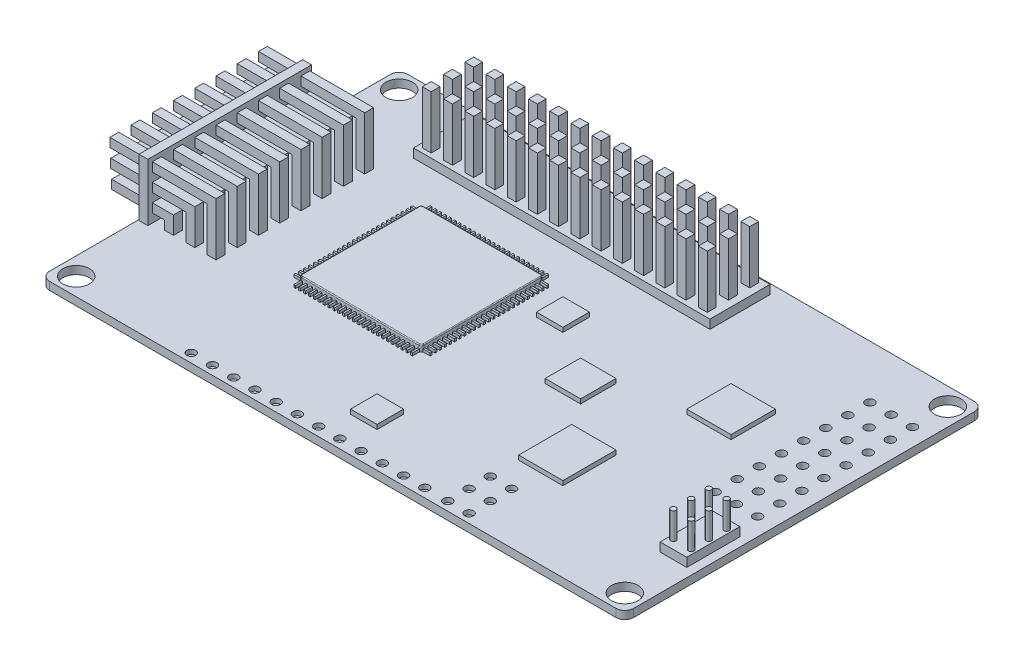
SolidWorks part; units mm, degrees
ref_plane "Спереди" through (0, 0, 0) normal (0, 0, 1) x (1, 0, 0)
ref_plane "Сверху" through (0, 0, 0) normal (0, 1, 0) x (1, 0, 0)
ref_plane "Справа" through (0, 0, 0) normal (1, 0, 0) x (0, 0, -1)
sketch "Эскиз1" plane through (0, 0, 0) normal (0, 1, 0) x (1, 0, 0)
  line L1 (-33, 20.25) -> (33, 20.25)
  line L2 (-33, 20.25) -> (-33, -20.25)
  line L3 (-33, -20.25) -> (33, -20.25)
  line L4 (33, 20.25) -> (33, -20.25)
  dimension "D1" = 66
  dimension "D2" = 40.5
  dimension "D3" = 33
  dimension "D4" = 20.25
extrude "Бобышка-Вытянуть1" add sketch "Эскиз1" along normal blind 0.9
sketch "Эскиз2" plane through (0, 0.9, 0) normal (0, 1, 0) x (1, 0, 0)
  line L0 (33, -20.25) -> (33, 20.25) construction
  line L1 (-17.8, 7.55) -> (-4, 7.55)
  line L2 (-17.8, 7.55) -> (-17.8, -6.25)
  line L3 (-17.8, -6.25) -> (-4, -6.25)
  line L4 (-4, 7.55) -> (-4, -6.25)
  line L5 (-33, -20.25) -> (33, -20.25) construction
  dimension "D1" = 13.8
  dimension "D2" = 13.8
  dimension "D3" = 37
  dimension "D4" = 14
extrude "Бобышка-Вытянуть2" add sketch "Эскиз2" along normal blind 0.7
sketch "Эскиз4" plane through (0, 0.9, 0) normal (0, 1, 0) x (1, 0, 0)
  line L2 (-28.1, -8.75) -> (-27.1, -8.75)
  line L3 (-30.5, -7.75) -> (-29.5, -7.75)
  line L4 (-30.5, -7.75) -> (-30.5, -8.75)
  line L5 (-30.5, -8.75) -> (-29.5, -8.75)
  line L6 (-29.5, -7.75) -> (-29.5, -8.75)
  line L7 (-27.1, -7.75) -> (-27.1, -8.75)
  line L8 (-28.1, -7.75) -> (-27.1, -7.75)
  line L9 (-28.1, -7.75) -> (-28.1, -8.75)
  line L10 (-25.7, -8.75) -> (-24.7, -8.75)
  line L11 (-24.7, -7.75) -> (-24.7, -8.75)
  line L12 (-25.7, -7.75) -> (-24.7, -7.75)
  line L13 (-25.7, -7.75) -> (-25.7, -8.75)
  line L14 (-28.1, -6.35) -> (-27.1, -6.35)
  line L15 (-27.1, -5.35) -> (-27.1, -6.35)
  line L16 (-28.1, -5.35) -> (-27.1, -5.35)
  line L17 (-28.1, -5.35) -> (-28.1, -6.35)
  line L18 (-25.7, -6.35) -> (-24.7, -6.35)
  line L19 (-24.7, -5.35) -> (-24.7, -6.35)
  line L20 (-25.7, -5.35) -> (-24.7, -5.35)
  line L21 (-25.7, -5.35) -> (-25.7, -6.35)
  line L22 (-28.1, -3.95) -> (-27.1, -3.95)
  line L23 (-27.1, -2.95) -> (-27.1, -3.95)
  line L24 (-28.1, -2.95) -> (-27.1, -2.95)
  line L25 (-28.1, -2.95) -> (-28.1, -3.95)
  line L26 (-25.7, -3.95) -> (-24.7, -3.95)
  line L27 (-24.7, -2.95) -> (-24.7, -3.95)
  line L28 (-25.7, -2.95) -> (-24.7, -2.95)
  line L29 (-25.7, -2.95) -> (-25.7, -3.95)
  line L30 (-28.1, -1.55) -> (-27.1, -1.55)
  line L31 (-27.1, -0.55) -> (-27.1, -1.55)
  line L32 (-28.1, -0.55) -> (-27.1, -0.55)
  line L33 (-28.1, -0.55) -> (-28.1, -1.55)
  line L34 (-25.7, -1.55) -> (-24.7, -1.55)
  line L35 (-24.7, -0.55) -> (-24.7, -1.55)
  line L36 (-25.7, -0.55) -> (-24.7, -0.55)
  line L37 (-25.7, -0.55) -> (-25.7, -1.55)
  line L38 (-28.1, 0.85) -> (-27.1, 0.85)
  line L39 (-27.1, 1.85) -> (-27.1, 0.85)
  line L40 (-28.1, 1.85) -> (-27.1, 1.85)
  line L41 (-28.1, 1.85) -> (-28.1, 0.85)
  line L42 (-25.7, 0.85) -> (-24.7, 0.85)
  line L43 (-24.7, 1.85) -> (-24.7, 0.85)
  line L44 (-25.7, 1.85) -> (-24.7, 1.85)
  line L45 (-25.7, 1.85) -> (-25.7, 0.85)
  line L46 (-28.1, 3.25) -> (-27.1, 3.25)
  line L47 (-27.1, 4.25) -> (-27.1, 3.25)
  line L48 (-28.1, 4.25) -> (-27.1, 4.25)
  line L49 (-28.1, 4.25) -> (-28.1, 3.25)
  line L50 (-25.7, 3.25) -> (-24.7, 3.25)
  line L51 (-24.7, 4.25) -> (-24.7, 3.25)
  line L52 (-25.7, 4.25) -> (-24.7, 4.25)
  line L53 (-25.7, 4.25) -> (-25.7, 3.25)
  line L54 (-28.1, 5.65) -> (-27.1, 5.65)
  line L55 (-27.1, 6.65) -> (-27.1, 5.65)
  line L56 (-28.1, 6.65) -> (-27.1, 6.65)
  line L57 (-28.1, 6.65) -> (-28.1, 5.65)
  line L58 (-25.7, 5.65) -> (-24.7, 5.65)
  line L59 (-24.7, 6.65) -> (-24.7, 5.65)
  line L60 (-25.7, 6.65) -> (-24.7, 6.65)
  line L61 (-25.7, 6.65) -> (-25.7, 5.65)
  line L62 (-28.1, 8.05) -> (-27.1, 8.05)
  line L63 (-27.1, 9.05) -> (-27.1, 8.05)
  line L64 (-28.1, 9.05) -> (-27.1, 9.05)
  line L65 (-28.1, 9.05) -> (-28.1, 8.05)
  line L66 (-25.7, 8.05) -> (-24.7, 8.05)
  line L67 (-24.7, 9.05) -> (-24.7, 8.05)
  line L68 (-25.7, 9.05) -> (-24.7, 9.05)
  line L69 (-25.7, 9.05) -> (-25.7, 8.05)
  line L70 (-30.5, -6.35) -> (-29.5, -6.35)
  line L71 (-29.5, -5.35) -> (-29.5, -6.35)
  line L72 (-30.5, -5.35) -> (-29.5, -5.35)
  line L73 (-30.5, -5.35) -> (-30.5, -6.35)
  line L74 (-30.5, -3.95) -> (-29.5, -3.95)
  line L75 (-29.5, -2.95) -> (-29.5, -3.95)
  line L76 (-30.5, -2.95) -> (-29.5, -2.95)
  line L77 (-30.5, -2.95) -> (-30.5, -3.95)
  line L78 (-30.5, -1.55) -> (-29.5, -1.55)
  line L79 (-29.5, -0.55) -> (-29.5, -1.55)
  line L80 (-30.5, -0.55) -> (-29.5, -0.55)
  line L81 (-30.5, -0.55) -> (-30.5, -1.55)
  line L82 (-30.5, 0.85) -> (-29.5, 0.85)
  line L83 (-29.5, 1.85) -> (-29.5, 0.85)
  line L84 (-30.5, 1.85) -> (-29.5, 1.85)
  line L85 (-30.5, 1.85) -> (-30.5, 0.85)
  line L86 (-30.5, 3.25) -> (-29.5, 3.25)
  line L87 (-29.5, 4.25) -> (-29.5, 3.25)
  line L88 (-30.5, 4.25) -> (-29.5, 4.25)
  line L89 (-30.5, 4.25) -> (-30.5, 3.25)
  line L90 (-30.5, 5.65) -> (-29.5, 5.65)
  line L91 (-29.5, 6.65) -> (-29.5, 5.65)
  line L92 (-30.5, 6.65) -> (-29.5, 6.65)
  line L93 (-30.5, 6.65) -> (-30.5, 5.65)
  line L94 (-30.5, 8.05) -> (-29.5, 8.05)
  line L95 (-29.5, 9.05) -> (-29.5, 8.05)
  line L96 (-30.5, 9.05) -> (-29.5, 9.05)
  line L97 (-30.5, 9.05) -> (-30.5, 8.05)
  dimension "D1" = 11.5
  dimension "D2" = 2.5
  dimension "D3" = 8
  dimension "D4" = 1
  dimension "D5" = 1
extrude "Бобышка-Вытянуть3" add sketch "Эскиз4" along normal blind 2
sketch "Эскиз5" plane through (-30.5, 0, 0) normal (-1, 0, 0) x (0, 0, 1)
  line L0 (-8.05, 2.9) -> (-8.05, 0.9) construction
  line L1 (-9.05, 2.9) -> (-8.05, 2.9)
  line L2 (-9.05, 2.9) -> (-9.05, 1.9)
  line L3 (-9.05, 1.9) -> (-8.05, 1.9)
  line L4 (-8.05, 2.9) -> (-8.05, 1.9)
  line L5 (-6.65, 2.9) -> (-5.65, 2.9)
  line L6 (-6.65, 2.9) -> (-6.65, 1.9)
  line L7 (-6.65, 1.9) -> (-5.65, 1.9)
  line L8 (-5.65, 2.9) -> (-5.65, 1.9)
  line L9 (-4.25, 2.9) -> (-3.25, 2.9)
  line L10 (-4.25, 2.9) -> (-4.25, 1.9)
  line L11 (-4.25, 1.9) -> (-3.25, 1.9)
  line L12 (-3.25, 2.9) -> (-3.25, 1.9)
  line L13 (-1.85, 2.9) -> (-0.85, 2.9)
  line L14 (-1.85, 2.9) -> (-1.85, 1.9)
  line L15 (-1.85, 1.9) -> (-0.85, 1.9)
  line L16 (-0.85, 2.9) -> (-0.85, 1.9)
  line L17 (0.55, 2.9) -> (1.55, 2.9)
  line L18 (0.55, 2.9) -> (0.55, 1.9)
  line L19 (0.55, 1.9) -> (1.55, 1.9)
  line L20 (1.55, 2.9) -> (1.55, 1.9)
  line L21 (2.95, 2.9) -> (3.95, 2.9)
  line L22 (2.95, 2.9) -> (2.95, 1.9)
  line L23 (2.95, 1.9) -> (3.95, 1.9)
  line L24 (3.95, 2.9) -> (3.95, 1.9)
  line L25 (5.35, 2.9) -> (6.35, 2.9)
  line L26 (5.35, 2.9) -> (5.35, 1.9)
  line L27 (5.35, 1.9) -> (6.35, 1.9)
  line L28 (6.35, 2.9) -> (6.35, 1.9)
  line L29 (7.75, 2.9) -> (8.75, 2.9)
  line L30 (7.75, 2.9) -> (7.75, 1.9)
  line L31 (7.75, 1.9) -> (8.75, 1.9)
  line L32 (8.75, 2.9) -> (8.75, 1.9)
  dimension "D1" = 1
  dimension "D2" = 1
extrude "Бобышка-Вытянуть4" add sketch "Эскиз5" along normal blind 6
sketch "Эскиз6" plane through (0, 2.9, 0) normal (0, 1, 0) x (1, 0, 0)
  line L0 (-28.1, -5.35) -> (-28.1, -6.35)
  line L1 (-28.1, -7.75) -> (-27.1, -7.75)
  line L2 (-28.1, -7.75) -> (-28.1, -8.75)
  line L3 (-28.1, -8.75) -> (-27.1, -8.75)
  line L4 (-27.1, -7.75) -> (-27.1, -8.75)
  line L5 (-28.1, -5.35) -> (-27.1, -5.35)
  line L6 (-27.1, -5.35) -> (-27.1, -6.35)
  line L7 (-28.1, -6.35) -> (-27.1, -6.35)
  line L8 (-28.1, -2.95) -> (-28.1, -3.95)
  line L9 (-28.1, -2.95) -> (-27.1, -2.95)
  line L10 (-27.1, -2.95) -> (-27.1, -3.95)
  line L11 (-28.1, -3.95) -> (-27.1, -3.95)
  line L12 (-28.1, -0.55) -> (-28.1, -1.55)
  line L13 (-28.1, -0.55) -> (-27.1, -0.55)
  line L14 (-27.1, -0.55) -> (-27.1, -1.55)
  line L15 (-28.1, -1.55) -> (-27.1, -1.55)
  line L16 (-28.1, 1.85) -> (-28.1, 0.85)
  line L17 (-28.1, 1.85) -> (-27.1, 1.85)
  line L18 (-27.1, 1.85) -> (-27.1, 0.85)
  line L19 (-28.1, 0.85) -> (-27.1, 0.85)
  line L20 (-28.1, 4.25) -> (-28.1, 3.25)
  line L21 (-28.1, 4.25) -> (-27.1, 4.25)
  line L22 (-27.1, 4.25) -> (-27.1, 3.25)
  line L23 (-28.1, 3.25) -> (-27.1, 3.25)
  line L24 (-28.1, 6.65) -> (-28.1, 5.65)
  line L25 (-28.1, 6.65) -> (-27.1, 6.65)
  line L26 (-27.1, 6.65) -> (-27.1, 5.65)
  line L27 (-28.1, 5.65) -> (-27.1, 5.65)
  line L28 (-28.1, 9.05) -> (-28.1, 8.05)
  line L29 (-28.1, 9.05) -> (-27.1, 9.05)
  line L30 (-27.1, 9.05) -> (-27.1, 8.05)
  line L31 (-28.1, 8.05) -> (-27.1, 8.05)
  dimension "D1" = 8
extrude "Бобышка-Вытянуть5" add sketch "Эскиз6" along normal blind 2
sketch "Эскиз7" plane through (-28.1, 0, 0) normal (-1, 0, 0) x (0, 0, 1)
  line L0 (-8.05, 4.9) -> (-8.05, 0.9) construction
  line L1 (-9.05, 4.9) -> (-8.05, 4.9)
  line L2 (-9.05, 4.9) -> (-9.05, 3.8951)
  line L3 (-9.05, 3.8951) -> (-8.05, 3.8951)
  line L4 (-8.05, 4.9) -> (-8.05, 3.8951)
  line L5 (-6.65, 4.9) -> (-5.65, 4.9)
  line L6 (-6.65, 4.9) -> (-6.65, 3.8951)
  line L7 (-6.65, 3.8951) -> (-5.65, 3.8951)
  line L8 (-5.65, 4.9) -> (-5.65, 3.8951)
  line L9 (-4.25, 4.9) -> (-3.25, 4.9)
  line L10 (-4.25, 4.9) -> (-4.25, 3.8951)
  line L11 (-4.25, 3.8951) -> (-3.25, 3.8951)
  line L12 (-3.25, 4.9) -> (-3.25, 3.8951)
  line L13 (-1.85, 4.9) -> (-0.85, 4.9)
  line L14 (-1.85, 4.9) -> (-1.85, 3.8951)
  line L15 (-1.85, 3.8951) -> (-0.85, 3.8951)
  line L16 (-0.85, 4.9) -> (-0.85, 3.8951)
  line L17 (0.55, 4.9) -> (1.55, 4.9)
  line L18 (0.55, 4.9) -> (0.55, 3.8951)
  line L19 (0.55, 3.8951) -> (1.55, 3.8951)
  line L20 (1.55, 4.9) -> (1.55, 3.8951)
  line L21 (2.95, 4.9) -> (3.95, 4.9)
  line L22 (2.95, 4.9) -> (2.95, 3.8951)
  line L23 (2.95, 3.8951) -> (3.95, 3.8951)
  line L24 (3.95, 4.9) -> (3.95, 3.8951)
  line L25 (5.35, 4.9) -> (6.35, 4.9)
  line L26 (5.35, 4.9) -> (5.35, 3.8951)
  line L27 (5.35, 3.8951) -> (6.35, 3.8951)
  line L28 (6.35, 4.9) -> (6.35, 3.8951)
  line L29 (7.75, 4.9) -> (8.75, 4.9)
  line L30 (7.75, 4.9) -> (7.75, 3.8951)
  line L31 (7.75, 3.8951) -> (8.75, 3.8951)
  line L32 (8.75, 4.9) -> (8.75, 3.8951)
  dimension "D1" = 1.0049
extrude "Бобышка-Вытянуть6" add sketch "Эскиз7" along normal blind 8.5
sketch "Эскиз8" plane through (0, 2.9, 0) normal (0, 1, 0) x (1, 0, 0)
  line L0 (-25.7, -5.35) -> (-25.7, -6.35)
  line L1 (-25.7, -7.75) -> (-24.7, -7.75)
  line L2 (-25.7, -7.75) -> (-25.7, -8.75)
  line L3 (-25.7, -8.75) -> (-24.7, -8.75)
  line L4 (-24.7, -7.75) -> (-24.7, -8.75)
  line L5 (-25.7, -5.35) -> (-24.7, -5.35)
  line L6 (-24.7, -5.35) -> (-24.7, -6.35)
  line L7 (-25.7, -6.35) -> (-24.7, -6.35)
  line L8 (-25.7, -2.95) -> (-25.7, -3.95)
  line L9 (-25.7, -2.95) -> (-24.7, -2.95)
  line L10 (-24.7, -2.95) -> (-24.7, -3.95)
  line L11 (-25.7, -3.95) -> (-24.7, -3.95)
  line L12 (-25.7, -0.55) -> (-25.7, -1.55)
  line L13 (-25.7, -0.55) -> (-24.7, -0.55)
  line L14 (-24.7, -0.55) -> (-24.7, -1.55)
  line L15 (-25.7, -1.55) -> (-24.7, -1.55)
  line L16 (-25.7, 1.85) -> (-25.7, 0.85)
  line L17 (-25.7, 1.85) -> (-24.7, 1.85)
  line L18 (-24.7, 1.85) -> (-24.7, 0.85)
  line L19 (-25.7, 0.85) -> (-24.7, 0.85)
  line L20 (-25.7, 4.25) -> (-25.7, 3.25)
  line L21 (-25.7, 4.25) -> (-24.7, 4.25)
  line L22 (-24.7, 4.25) -> (-24.7, 3.25)
  line L23 (-25.7, 3.25) -> (-24.7, 3.25)
  line L24 (-25.7, 6.65) -> (-25.7, 5.65)
  line L25 (-25.7, 6.65) -> (-24.7, 6.65)
  line L26 (-24.7, 6.65) -> (-24.7, 5.65)
  line L27 (-25.7, 5.65) -> (-24.7, 5.65)
  line L28 (-25.7, 9.05) -> (-25.7, 8.05)
  line L29 (-25.7, 9.05) -> (-24.7, 9.05)
  line L30 (-24.7, 9.05) -> (-24.7, 8.05)
  line L31 (-25.7, 8.05) -> (-24.7, 8.05)
  dimension "D1" = 8
extrude "Бобышка-Вытянуть7" add sketch "Эскиз8" along normal blind 4
sketch "Эскиз9" plane through (-25.7, 0, 0) normal (-1, 0, 0) x (0, 0, 1)
  line L0 (-8.05, 6.9) -> (-8.05, 0.9) construction
  line L1 (-9.05, 6.9) -> (-8.05, 6.9)
  line L2 (-9.05, 6.9) -> (-9.05, 5.8969)
  line L3 (-9.05, 5.8969) -> (-8.05, 5.8969)
  line L4 (-8.05, 6.9) -> (-8.05, 5.8969)
  line L5 (-6.65, 6.9) -> (-5.65, 6.9)
  line L6 (-6.65, 6.9) -> (-6.65, 5.8969)
  line L7 (-6.65, 5.8969) -> (-5.65, 5.8969)
  line L8 (-5.65, 6.9) -> (-5.65, 5.8969)
  line L9 (-4.25, 6.9) -> (-3.25, 6.9)
  line L10 (-4.25, 6.9) -> (-4.25, 5.8969)
  line L11 (-4.25, 5.8969) -> (-3.25, 5.8969)
  line L12 (-3.25, 6.9) -> (-3.25, 5.8969)
  line L13 (-1.85, 6.9) -> (-0.85, 6.9)
  line L14 (-1.85, 6.9) -> (-1.85, 5.8969)
  line L15 (-1.85, 5.8969) -> (-0.85, 5.8969)
  line L16 (-0.85, 6.9) -> (-0.85, 5.8969)
  line L17 (0.55, 6.9) -> (1.55, 6.9)
  line L18 (0.55, 6.9) -> (0.55, 5.8969)
  line L19 (0.55, 5.8969) -> (1.55, 5.8969)
  line L20 (1.55, 6.9) -> (1.55, 5.8969)
  line L21 (2.95, 6.9) -> (3.95, 6.9)
  line L22 (2.95, 6.9) -> (2.95, 5.8969)
  line L23 (2.95, 5.8969) -> (3.95, 5.8969)
  line L24 (3.95, 6.9) -> (3.95, 5.8969)
  line L25 (5.35, 6.9) -> (6.35, 6.9)
  line L26 (5.35, 6.9) -> (5.35, 5.8969)
  line L27 (5.35, 5.8969) -> (6.35, 5.8969)
  line L28 (6.35, 6.9) -> (6.35, 5.8969)
  line L29 (7.75, 6.9) -> (8.75, 6.9)
  line L30 (7.75, 6.9) -> (7.75, 5.8969)
  line L31 (7.75, 5.8969) -> (8.75, 5.8969)
  line L32 (8.75, 6.9) -> (8.75, 5.8969)
  dimension "D1" = 1.0031
extrude "Бобышка-Вытянуть8" add sketch "Эскиз9" along normal blind 11
sketch "Эскиз10" plane through (0, 0, 8.75) normal (0, 0, 1) x (1, 0, 0)
  line L1 (-31.9, 0.9) -> (-32.9, 0.9)
  line L2 (-32.9, 0.9) -> (-32.9, 7.3945)
  line L4 (-32.9, 7.3945) -> (-31.9, 7.3945)
  line L5 (-31.9, 0.9) -> (-31.9, 7.3945)
  dimension "D1" = 1
  dimension "D2" = 1
  dimension "D3" = 0.1
extrude "Бобышка-Вытянуть10" add sketch "Эскиз10" along normal blind 0.5 and the other way blind 18
sketch "Эскиз11" plane through (0, 0.9, 0) normal (0, 1, 0) x (1, 0, 0)
  line L0 (-20.6, 18.6656) -> (-19.6, 18.6656)
  line L1 (-23, 18.6656) -> (-22, 18.6656)
  line L2 (-23, 18.6656) -> (-23, 17.6656)
  line L3 (-23, 17.6656) -> (-22, 17.6656)
  line L4 (-22, 18.6656) -> (-22, 17.6656)
  line L5 (-19.6, 18.6656) -> (-19.6, 17.6656)
  line L6 (-20.6, 17.6656) -> (-19.6, 17.6656)
  line L7 (-20.6, 18.6656) -> (-20.6, 17.6656)
  line L8 (-18.2, 18.6656) -> (-17.2, 18.6656)
  line L9 (-17.2, 18.6656) -> (-17.2, 17.6656)
  line L10 (-18.2, 17.6656) -> (-17.2, 17.6656)
  line L11 (-18.2, 18.6656) -> (-18.2, 17.6656)
  line L12 (-15.8, 18.6656) -> (-14.8, 18.6656)
  line L13 (-14.8, 18.6656) -> (-14.8, 17.6656)
  line L14 (-15.8, 17.6656) -> (-14.8, 17.6656)
  line L15 (-15.8, 18.6656) -> (-15.8, 17.6656)
  line L16 (-13.4, 18.6656) -> (-12.4, 18.6656)
  line L17 (-12.4, 18.6656) -> (-12.4, 17.6656)
  line L18 (-13.4, 17.6656) -> (-12.4, 17.6656)
  line L19 (-13.4, 18.6656) -> (-13.4, 17.6656)
  line L20 (-11, 18.6656) -> (-10, 18.6656)
  line L21 (-10, 18.6656) -> (-10, 17.6656)
  line L22 (-11, 17.6656) -> (-10, 17.6656)
  line L23 (-11, 18.6656) -> (-11, 17.6656)
  line L24 (-8.6, 18.6656) -> (-7.6, 18.6656)
  line L25 (-7.6, 18.6656) -> (-7.6, 17.6656)
  line L26 (-8.6, 17.6656) -> (-7.6, 17.6656)
  line L27 (-8.6, 18.6656) -> (-8.6, 17.6656)
  line L28 (-6.2, 18.6656) -> (-5.2, 18.6656)
  line L29 (-5.2, 18.6656) -> (-5.2, 17.6656)
  line L30 (-6.2, 17.6656) -> (-5.2, 17.6656)
  line L31 (-6.2, 18.6656) -> (-6.2, 17.6656)
  line L32 (-3.8, 18.6656) -> (-2.8, 18.6656)
  line L33 (-2.8, 18.6656) -> (-2.8, 17.6656)
  line L34 (-3.8, 17.6656) -> (-2.8, 17.6656)
  line L35 (-3.8, 18.6656) -> (-3.8, 17.6656)
  line L36 (-1.4, 18.6656) -> (-0.4, 18.6656)
  line L37 (-0.4, 18.6656) -> (-0.4, 17.6656)
  line L38 (-1.4, 17.6656) -> (-0.4, 17.6656)
  line L39 (-1.4, 18.6656) -> (-1.4, 17.6656)
  line L40 (1, 18.6656) -> (2, 18.6656)
  line L41 (2, 18.6656) -> (2, 17.6656)
  line L42 (1, 17.6656) -> (2, 17.6656)
  line L43 (1, 18.6656) -> (1, 17.6656)
  line L44 (3.4, 18.6656) -> (4.4, 18.6656)
  line L45 (4.4, 18.6656) -> (4.4, 17.6656)
  line L46 (3.4, 17.6656) -> (4.4, 17.6656)
  line L47 (3.4, 18.6656) -> (3.4, 17.6656)
  line L48 (5.8, 18.6656) -> (6.8, 18.6656)
  line L49 (6.8, 18.6656) -> (6.8, 17.6656)
  line L50 (5.8, 17.6656) -> (6.8, 17.6656)
  line L51 (5.8, 18.6656) -> (5.8, 17.6656)
  line L52 (8.2, 18.6656) -> (9.2, 18.6656)
  line L53 (9.2, 18.6656) -> (9.2, 17.6656)
  line L54 (8.2, 17.6656) -> (9.2, 17.6656)
  line L55 (8.2, 18.6656) -> (8.2, 17.6656)
  line L56 (-20.6, 16.2656) -> (-19.6, 16.2656)
  line L57 (-19.6, 16.2656) -> (-19.6, 15.2656)
  line L58 (-20.6, 15.2656) -> (-19.6, 15.2656)
  line L59 (-20.6, 16.2656) -> (-20.6, 15.2656)
  line L60 (-18.2, 16.2656) -> (-17.2, 16.2656)
  line L61 (-17.2, 16.2656) -> (-17.2, 15.2656)
  line L62 (-18.2, 15.2656) -> (-17.2, 15.2656)
  line L63 (-18.2, 16.2656) -> (-18.2, 15.2656)
  line L64 (-15.8, 16.2656) -> (-14.8, 16.2656)
  line L65 (-14.8, 16.2656) -> (-14.8, 15.2656)
  line L66 (-15.8, 15.2656) -> (-14.8, 15.2656)
  line L67 (-15.8, 16.2656) -> (-15.8, 15.2656)
  line L68 (-13.4, 16.2656) -> (-12.4, 16.2656)
  line L69 (-12.4, 16.2656) -> (-12.4, 15.2656)
  line L70 (-13.4, 15.2656) -> (-12.4, 15.2656)
  line L71 (-13.4, 16.2656) -> (-13.4, 15.2656)
  line L72 (-11, 16.2656) -> (-10, 16.2656)
  line L73 (-10, 16.2656) -> (-10, 15.2656)
  line L74 (-11, 15.2656) -> (-10, 15.2656)
  line L75 (-11, 16.2656) -> (-11, 15.2656)
  line L76 (-8.6, 16.2656) -> (-7.6, 16.2656)
  line L77 (-7.6, 16.2656) -> (-7.6, 15.2656)
  line L78 (-8.6, 15.2656) -> (-7.6, 15.2656)
  line L79 (-8.6, 16.2656) -> (-8.6, 15.2656)
  line L80 (-6.2, 16.2656) -> (-5.2, 16.2656)
  line L81 (-5.2, 16.2656) -> (-5.2, 15.2656)
  line L82 (-6.2, 15.2656) -> (-5.2, 15.2656)
  line L83 (-6.2, 16.2656) -> (-6.2, 15.2656)
  line L84 (-3.8, 16.2656) -> (-2.8, 16.2656)
  line L85 (-2.8, 16.2656) -> (-2.8, 15.2656)
  line L86 (-3.8, 15.2656) -> (-2.8, 15.2656)
  line L87 (-3.8, 16.2656) -> (-3.8, 15.2656)
  line L88 (-1.4, 16.2656) -> (-0.4, 16.2656)
  line L89 (-0.4, 16.2656) -> (-0.4, 15.2656)
  line L90 (-1.4, 15.2656) -> (-0.4, 15.2656)
  line L91 (-1.4, 16.2656) -> (-1.4, 15.2656)
  line L92 (1, 16.2656) -> (2, 16.2656)
  line L93 (2, 16.2656) -> (2, 15.2656)
  line L94 (1, 15.2656) -> (2, 15.2656)
  line L95 (1, 16.2656) -> (1, 15.2656)
  line L96 (3.4, 16.2656) -> (4.4, 16.2656)
  line L97 (4.4, 16.2656) -> (4.4, 15.2656)
  line L98 (3.4, 15.2656) -> (4.4, 15.2656)
  line L99 (3.4, 16.2656) -> (3.4, 15.2656)
  line L100 (5.8, 16.2656) -> (6.8, 16.2656)
  line L101 (6.8, 16.2656) -> (6.8, 15.2656)
  line L102 (5.8, 15.2656) -> (6.8, 15.2656)
  line L103 (5.8, 16.2656) -> (5.8, 15.2656)
  line L104 (8.2, 16.2656) -> (9.2, 16.2656)
  line L105 (9.2, 16.2656) -> (9.2, 15.2656)
  line L106 (8.2, 15.2656) -> (9.2, 15.2656)
  line L107 (8.2, 16.2656) -> (8.2, 15.2656)
  line L108 (-20.6, 13.8656) -> (-19.6, 13.8656)
  line L109 (-19.6, 13.8656) -> (-19.6, 12.8656)
  line L110 (-20.6, 12.8656) -> (-19.6, 12.8656)
  line L111 (-20.6, 13.8656) -> (-20.6, 12.8656)
  line L112 (-18.2, 13.8656) -> (-17.2, 13.8656)
  line L113 (-17.2, 13.8656) -> (-17.2, 12.8656)
  line L114 (-18.2, 12.8656) -> (-17.2, 12.8656)
  line L115 (-18.2, 13.8656) -> (-18.2, 12.8656)
  line L116 (-15.8, 13.8656) -> (-14.8, 13.8656)
  line L117 (-14.8, 13.8656) -> (-14.8, 12.8656)
  line L118 (-15.8, 12.8656) -> (-14.8, 12.8656)
  line L119 (-15.8, 13.8656) -> (-15.8, 12.8656)
  line L120 (-13.4, 13.8656) -> (-12.4, 13.8656)
  line L121 (-12.4, 13.8656) -> (-12.4, 12.8656)
  line L122 (-13.4, 12.8656) -> (-12.4, 12.8656)
  line L123 (-13.4, 13.8656) -> (-13.4, 12.8656)
  line L124 (-11, 13.8656) -> (-10, 13.8656)
  line L125 (-10, 13.8656) -> (-10, 12.8656)
  line L126 (-11, 12.8656) -> (-10, 12.8656)
  line L127 (-11, 13.8656) -> (-11, 12.8656)
  line L128 (-8.6, 13.8656) -> (-7.6, 13.8656)
  line L129 (-7.6, 13.8656) -> (-7.6, 12.8656)
  line L130 (-8.6, 12.8656) -> (-7.6, 12.8656)
  line L131 (-8.6, 13.8656) -> (-8.6, 12.8656)
  line L132 (-6.2, 13.8656) -> (-5.2, 13.8656)
  line L133 (-5.2, 13.8656) -> (-5.2, 12.8656)
  line L134 (-6.2, 12.8656) -> (-5.2, 12.8656)
  line L135 (-6.2, 13.8656) -> (-6.2, 12.8656)
  line L136 (-3.8, 13.8656) -> (-2.8, 13.8656)
  line L137 (-2.8, 13.8656) -> (-2.8, 12.8656)
  line L138 (-3.8, 12.8656) -> (-2.8, 12.8656)
  line L139 (-3.8, 13.8656) -> (-3.8, 12.8656)
  line L140 (-1.4, 13.8656) -> (-0.4, 13.8656)
  line L141 (-0.4, 13.8656) -> (-0.4, 12.8656)
  line L142 (-1.4, 12.8656) -> (-0.4, 12.8656)
  line L143 (-1.4, 13.8656) -> (-1.4, 12.8656)
  line L144 (1, 13.8656) -> (2, 13.8656)
  line L145 (2, 13.8656) -> (2, 12.8656)
  line L146 (1, 12.8656) -> (2, 12.8656)
  line L147 (1, 13.8656) -> (1, 12.8656)
  line L148 (3.4, 13.8656) -> (4.4, 13.8656)
  line L149 (4.4, 13.8656) -> (4.4, 12.8656)
  line L150 (3.4, 12.8656) -> (4.4, 12.8656)
  line L151 (3.4, 13.8656) -> (3.4, 12.8656)
  line L152 (5.8, 13.8656) -> (6.8, 13.8656)
  line L153 (6.8, 13.8656) -> (6.8, 12.8656)
  line L154 (5.8, 12.8656) -> (6.8, 12.8656)
  line L155 (5.8, 13.8656) -> (5.8, 12.8656)
  line L156 (8.2, 13.8656) -> (9.2, 13.8656)
  line L157 (9.2, 13.8656) -> (9.2, 12.8656)
  line L158 (8.2, 12.8656) -> (9.2, 12.8656)
  line L159 (8.2, 13.8656) -> (8.2, 12.8656)
  line L160 (-23, 16.2656) -> (-22, 16.2656)
  line L161 (-22, 16.2656) -> (-22, 15.2656)
  line L162 (-23, 15.2656) -> (-22, 15.2656)
  line L163 (-23, 16.2656) -> (-23, 15.2656)
  line L164 (-23, 13.8656) -> (-22, 13.8656)
  line L165 (-22, 13.8656) -> (-22, 12.8656)
  line L166 (-23, 12.8656) -> (-22, 12.8656)
  line L167 (-23, 13.8656) -> (-23, 12.8656)
  dimension "D1" = 1
  dimension "D2" = 1
  dimension "D3" = 10
  dimension "D4" = 3
extrude "Бобышка-Вытянуть11" add sketch "Эскиз11" along normal blind 7
sketch "Эскиз12" plane through (-23, 0, 0) normal (-1, 0, 0) x (0, 0, 1)
  line L0 (-20.25, 0.9) -> (20.25, 0.9) construction
  line L1 (-19.1656, 1.9) -> (-12.3656, 1.9)
  line L2 (-19.1656, 1.9) -> (-19.1656, 0.9)
  line L3 (-19.1656, 0.9) -> (-12.3656, 0.9)
  line L4 (-12.3656, 1.9) -> (-12.3656, 0.9)
  line L5 (-18.6656, 7.9) -> (-18.6656, 0.9) construction
  line L6 (-12.8656, 7.9) -> (-12.8656, 0.9) construction
  dimension "D1" = 1
  dimension "D2" = 0.5
  dimension "D3" = 0.5
extrude "Бобышка-Вытянуть12" add sketch "Эскиз12" along normal blind 0.5 and the other way blind 33
sketch "Эскиз13" plane through (0, 0.9, 0) normal (0, 1, 0) x (1, 0, 0)
  line L0 (33, -20.25) -> (33, 20.25) construction
  line L1 (33, 20.25) -> (-33, 20.25) construction
  circle A0 centre (31, 14.25) radius 0.5
  circle A1 centre (28.6, 14.25) radius 0.5
  circle A2 centre (26.2, 14.25) radius 0.5
  circle A3 centre (28.6, 11.75) radius 0.5
  circle A4 centre (26.2, 11.75) radius 0.5
  circle A5 centre (28.6, 9.25) radius 0.5
  circle A6 centre (26.2, 9.25) radius 0.5
  circle A7 centre (28.6, 6.75) radius 0.5
  circle A8 centre (26.2, 6.75) radius 0.5
  circle A9 centre (28.6, 4.25) radius 0.5
  circle A10 centre (26.2, 4.25) radius 0.5
  circle A11 centre (28.6, 1.75) radius 0.5
  circle A12 centre (26.2, 1.75) radius 0.5
  circle A13 centre (28.6, -0.75) radius 0.5
  circle A14 centre (26.2, -0.75) radius 0.5
  circle A15 centre (28.6, -3.25) radius 0.5
  circle A16 centre (26.2, -3.25) radius 0.5
  circle A17 centre (31, 11.75) radius 0.5
  circle A18 centre (31, 9.25) radius 0.5
  circle A19 centre (31, 6.75) radius 0.5
  circle A20 centre (31, 4.25) radius 0.5
  circle A21 centre (31, 1.75) radius 0.5
  circle A22 centre (31, -0.75) radius 0.5
  circle A23 centre (31, -3.25) radius 0.5
  dimension "D1" = 1
  dimension "D2" = 2
  dimension "D3" = 6
  dimension "D4" = 8
extrude "Вырез-Вытянуть1" cut sketch "Эскиз13" against normal blind 2
sketch "Эскиз14" plane through (0, 0.9, 0) normal (0, 1, 0) x (1, 0, 0)
  line L0 (33, 20.25) -> (-33, 20.25) construction
  line L1 (-33, 20.25) -> (-33, -20.25) construction
  circle A0 centre (-31, 18.25) radius 1.5
  circle A1 centre (31, 18.25) radius 1.5
  circle A2 centre (31, -18.25) radius 1.5
  circle A3 centre (-31, -18.25) radius 1.5
  dimension "D1" = 3
  dimension "D2" = 2
  dimension "D3" = 2
  dimension "D4" = 2
extrude "Вырез-Вытянуть2" cut sketch "Эскиз14" against normal blind 1
sketch "Эскиз15" plane through (0, 0.9, 0) normal (0, 1, 0) x (1, 0, 0)
  line L0 (33, -20.25) -> (33, 20.25) construction
  line L1 (-33, -20.25) -> (33, -20.25) construction
  circle A0 centre (31.5, -11.25) radius 0.3
  circle A1 centre (29.5, -11.25) radius 0.3
  circle A2 centre (29.5, -9.25) radius 0.3
  circle A3 centre (29.5, -7.25) radius 0.3
  circle A4 centre (31.5, -9.25) radius 0.3
  circle A5 centre (31.5, -7.25) radius 0.3
  dimension "D1" = 0.6
  dimension "D2" = 1.5
  dimension "D3" = 9
  dimension "D4" = 3
extrude "Бобышка-Вытянуть13" add sketch "Эскиз15" along normal blind 4
sketch "Эскиз16" plane through (0, 0.9, 0) normal (0, 1, 0) x (1, 0, 0)
  line L0 (33, -20.25) -> (33, 20.25) construction
  line L1 (29, -6.25) -> (32, -6.25)
  line L2 (29, -6.25) -> (29, -12.25)
  line L3 (29, -12.25) -> (32, -12.25)
  line L4 (32, -6.25) -> (32, -12.25)
  dimension "D1" = 3
  dimension "D2" = 6
  dimension "D3" = 1
  dimension "D4" = 8
extrude "Бобышка-Вытянуть14" add sketch "Эскиз16" along normal blind 1
sketch "Эскиз17" plane through (0, 0.9, 0) normal (0, 1, 0) x (1, 0, 0)
  line L0 (-17.05, 8.35) -> (-16.85, 8.35)
  line L1 (-17.6, 8.35) -> (-17.4, 8.35)
  line L2 (-17.6, 8.35) -> (-17.6, -7.05)
  line L3 (-17.6, -7.05) -> (-17.4, -7.05)
  line L4 (-17.4, 8.35) -> (-17.4, -7.05)
  line L5 (-17.05, 8.35) -> (-17.05, -7.05)
  line L6 (-17.05, -7.05) -> (-16.85, -7.05)
  line L7 (-16.85, 8.35) -> (-16.85, -7.05)
  line L8 (-16.5, 8.35) -> (-16.3, 8.35)
  line L9 (-16.5, 8.35) -> (-16.5, -7.05)
  line L10 (-16.5, -7.05) -> (-16.3, -7.05)
  line L11 (-16.3, 8.35) -> (-16.3, -7.05)
  line L12 (-15.95, 8.35) -> (-15.75, 8.35)
  line L13 (-15.95, 8.35) -> (-15.95, -7.05)
  line L14 (-15.95, -7.05) -> (-15.75, -7.05)
  line L15 (-15.75, 8.35) -> (-15.75, -7.05)
  line L16 (-15.4, 8.35) -> (-15.2, 8.35)
  line L17 (-15.4, 8.35) -> (-15.4, -7.05)
  line L18 (-15.4, -7.05) -> (-15.2, -7.05)
  line L19 (-15.2, 8.35) -> (-15.2, -7.05)
  line L20 (-14.85, 8.35) -> (-14.65, 8.35)
  line L21 (-14.85, 8.35) -> (-14.85, -7.05)
  line L22 (-14.85, -7.05) -> (-14.65, -7.05)
  line L23 (-14.65, 8.35) -> (-14.65, -7.05)
  line L24 (-14.3, 8.35) -> (-14.1, 8.35)
  line L25 (-14.3, 8.35) -> (-14.3, -7.05)
  line L26 (-14.3, -7.05) -> (-14.1, -7.05)
  line L27 (-14.1, 8.35) -> (-14.1, -7.05)
  line L28 (-13.75, 8.35) -> (-13.55, 8.35)
  line L29 (-13.75, 8.35) -> (-13.75, -7.05)
  line L30 (-13.75, -7.05) -> (-13.55, -7.05)
  line L31 (-13.55, 8.35) -> (-13.55, -7.05)
  line L32 (-13.2, 8.35) -> (-13, 8.35)
  line L33 (-13.2, 8.35) -> (-13.2, -7.05)
  line L34 (-13.2, -7.05) -> (-13, -7.05)
  line L35 (-13, 8.35) -> (-13, -7.05)
  line L36 (-12.65, 8.35) -> (-12.45, 8.35)
  line L37 (-12.65, 8.35) -> (-12.65, -7.05)
  line L38 (-12.65, -7.05) -> (-12.45, -7.05)
  line L39 (-12.45, 8.35) -> (-12.45, -7.05)
  line L40 (-12.1, 8.35) -> (-11.9, 8.35)
  line L41 (-12.1, 8.35) -> (-12.1, -7.05)
  line L42 (-12.1, -7.05) -> (-11.9, -7.05)
  line L43 (-11.9, 8.35) -> (-11.9, -7.05)
  line L44 (-11.55, 8.35) -> (-11.35, 8.35)
  line L45 (-11.55, 8.35) -> (-11.55, -7.05)
  line L46 (-11.55, -7.05) -> (-11.35, -7.05)
  line L47 (-11.35, 8.35) -> (-11.35, -7.05)
  line L48 (-11, 8.35) -> (-10.8, 8.35)
  line L49 (-11, 8.35) -> (-11, -7.05)
  line L50 (-11, -7.05) -> (-10.8, -7.05)
  line L51 (-10.8, 8.35) -> (-10.8, -7.05)
  line L52 (-10.45, 8.35) -> (-10.25, 8.35)
  line L53 (-10.45, 8.35) -> (-10.45, -7.05)
  line L54 (-10.45, -7.05) -> (-10.25, -7.05)
  line L55 (-10.25, 8.35) -> (-10.25, -7.05)
  line L56 (-9.9, 8.35) -> (-9.7, 8.35)
  line L57 (-9.9, 8.35) -> (-9.9, -7.05)
  line L58 (-9.9, -7.05) -> (-9.7, -7.05)
  line L59 (-9.7, 8.35) -> (-9.7, -7.05)
  line L60 (-9.35, 8.35) -> (-9.15, 8.35)
  line L61 (-9.35, 8.35) -> (-9.35, -7.05)
  line L62 (-9.35, -7.05) -> (-9.15, -7.05)
  line L63 (-9.15, 8.35) -> (-9.15, -7.05)
  line L64 (-8.8, 8.35) -> (-8.6, 8.35)
  line L65 (-8.8, 8.35) -> (-8.8, -7.05)
  line L66 (-8.8, -7.05) -> (-8.6, -7.05)
  line L67 (-8.6, 8.35) -> (-8.6, -7.05)
  line L68 (-8.25, 8.35) -> (-8.05, 8.35)
  line L69 (-8.25, 8.35) -> (-8.25, -7.05)
  line L70 (-8.25, -7.05) -> (-8.05, -7.05)
  line L71 (-8.05, 8.35) -> (-8.05, -7.05)
  line L72 (-7.7, 8.35) -> (-7.5, 8.35)
  line L73 (-7.7, 8.35) -> (-7.7, -7.05)
  line L74 (-7.7, -7.05) -> (-7.5, -7.05)
  line L75 (-7.5, 8.35) -> (-7.5, -7.05)
  line L76 (-7.15, 8.35) -> (-6.95, 8.35)
  line L77 (-7.15, 8.35) -> (-7.15, -7.05)
  line L78 (-7.15, -7.05) -> (-6.95, -7.05)
  line L79 (-6.95, 8.35) -> (-6.95, -7.05)
  line L80 (-6.6, 8.35) -> (-6.4, 8.35)
  line L81 (-6.6, 8.35) -> (-6.6, -7.05)
  line L82 (-6.6, -7.05) -> (-6.4, -7.05)
  line L83 (-6.4, 8.35) -> (-6.4, -7.05)
  line L84 (-6.05, 8.35) -> (-5.85, 8.35)
  line L85 (-6.05, 8.35) -> (-6.05, -7.05)
  line L86 (-6.05, -7.05) -> (-5.85, -7.05)
  line L87 (-5.85, 8.35) -> (-5.85, -7.05)
  line L88 (-5.5, 8.35) -> (-5.3, 8.35)
  line L89 (-5.5, 8.35) -> (-5.5, -7.05)
  line L90 (-5.5, -7.05) -> (-5.3, -7.05)
  line L91 (-5.3, 8.35) -> (-5.3, -7.05)
  line L92 (-4.95, 8.35) -> (-4.75, 8.35)
  line L93 (-4.95, 8.35) -> (-4.95, -7.05)
  line L94 (-4.95, -7.05) -> (-4.75, -7.05)
  line L95 (-4.75, 8.35) -> (-4.75, -7.05)
  line L96 (-4.4, 8.35) -> (-4.2, 8.35)
  line L97 (-4.4, 8.35) -> (-4.4, -7.05)
  line L98 (-4.4, -7.05) -> (-4.2, -7.05)
  line L99 (-4.2, 8.35) -> (-4.2, -7.05)
  dimension "D1" = 0.2
  dimension "D2" = 0.2
  dimension "D3" = 0.8
  dimension "D4" = 0.8
extrude "Бобышка-Вытянуть15" add sketch "Эскиз17" along normal blind 0.3
sketch "Эскиз18" plane through (0, 0.9, 0) normal (0, 1, 0) x (1, 0, 0)
  line L0 (-17.6, 7.55) -> (-17.8, 7.55) construction
  line L1 (-18.6, 7.35) -> (-3.2, 7.35)
  line L2 (-18.6, 7.35) -> (-18.6, 7.15)
  line L3 (-18.6, 7.15) -> (-3.2, 7.15)
  line L4 (-3.2, 7.35) -> (-3.2, 7.15)
  line L5 (-17.8, 7.55) -> (-17.8, -6.25) construction
  line L6 (-4, -6.25) -> (-4, 7.55) construction
  line L7 (-18.6, 6.8) -> (-3.2, 6.8)
  line L8 (-18.6, 6.6) -> (-3.2, 6.6)
  line L9 (-3.2, 6.8) -> (-3.2, 6.6)
  line L10 (-18.6, 6.8) -> (-18.6, 6.6)
  line L11 (-18.6, 6.25) -> (-3.2, 6.25)
  line L12 (-18.6, 6.05) -> (-3.2, 6.05)
  line L13 (-3.2, 6.25) -> (-3.2, 6.05)
  line L14 (-18.6, 6.25) -> (-18.6, 6.05)
  line L15 (-18.6, 5.7) -> (-3.2, 5.7)
  line L16 (-18.6, 5.5) -> (-3.2, 5.5)
  line L17 (-3.2, 5.7) -> (-3.2, 5.5)
  line L18 (-18.6, 5.7) -> (-18.6, 5.5)
  line L19 (-18.6, 5.15) -> (-3.2, 5.15)
  line L20 (-18.6, 4.95) -> (-3.2, 4.95)
  line L21 (-3.2, 5.15) -> (-3.2, 4.95)
  line L22 (-18.6, 5.15) -> (-18.6, 4.95)
  line L23 (-18.6, 4.6) -> (-3.2, 4.6)
  line L24 (-18.6, 4.4) -> (-3.2, 4.4)
  line L25 (-3.2, 4.6) -> (-3.2, 4.4)
  line L26 (-18.6, 4.6) -> (-18.6, 4.4)
  line L27 (-18.6, 4.05) -> (-3.2, 4.05)
  line L28 (-18.6, 3.85) -> (-3.2, 3.85)
  line L29 (-3.2, 4.05) -> (-3.2, 3.85)
  line L30 (-18.6, 4.05) -> (-18.6, 3.85)
  line L31 (-18.6, 3.5) -> (-3.2, 3.5)
  line L32 (-18.6, 3.3) -> (-3.2, 3.3)
  line L33 (-3.2, 3.5) -> (-3.2, 3.3)
  line L34 (-18.6, 3.5) -> (-18.6, 3.3)
  line L35 (-18.6, 2.95) -> (-3.2, 2.95)
  line L36 (-18.6, 2.75) -> (-3.2, 2.75)
  line L37 (-3.2, 2.95) -> (-3.2, 2.75)
  line L38 (-18.6, 2.95) -> (-18.6, 2.75)
  line L39 (-18.6, 2.4) -> (-3.2, 2.4)
  line L40 (-18.6, 2.2) -> (-3.2, 2.2)
  line L41 (-3.2, 2.4) -> (-3.2, 2.2)
  line L42 (-18.6, 2.4) -> (-18.6, 2.2)
  line L43 (-18.6, 1.85) -> (-3.2, 1.85)
  line L44 (-18.6, 1.65) -> (-3.2, 1.65)
  line L45 (-3.2, 1.85) -> (-3.2, 1.65)
  line L46 (-18.6, 1.85) -> (-18.6, 1.65)
  line L47 (-18.6, 1.3) -> (-3.2, 1.3)
  line L48 (-18.6, 1.1) -> (-3.2, 1.1)
  line L49 (-3.2, 1.3) -> (-3.2, 1.1)
  line L50 (-18.6, 1.3) -> (-18.6, 1.1)
  line L51 (-18.6, 0.75) -> (-3.2, 0.75)
  line L52 (-18.6, 0.55) -> (-3.2, 0.55)
  line L53 (-3.2, 0.75) -> (-3.2, 0.55)
  line L54 (-18.6, 0.75) -> (-18.6, 0.55)
  line L55 (-18.6, 0.2) -> (-3.2, 0.2)
  line L56 (-18.6, 0) -> (-3.2, 0)
  line L57 (-3.2, 0.2) -> (-3.2, 0)
  line L58 (-18.6, 0.2) -> (-18.6, 0)
  line L59 (-18.6, -0.35) -> (-3.2, -0.35)
  line L60 (-18.6, -0.55) -> (-3.2, -0.55)
  line L61 (-3.2, -0.35) -> (-3.2, -0.55)
  line L62 (-18.6, -0.35) -> (-18.6, -0.55)
  line L63 (-18.6, -0.9) -> (-3.2, -0.9)
  line L64 (-18.6, -1.1) -> (-3.2, -1.1)
  line L65 (-3.2, -0.9) -> (-3.2, -1.1)
  line L66 (-18.6, -0.9) -> (-18.6, -1.1)
  line L67 (-18.6, -1.45) -> (-3.2, -1.45)
  line L68 (-18.6, -1.65) -> (-3.2, -1.65)
  line L69 (-3.2, -1.45) -> (-3.2, -1.65)
  line L70 (-18.6, -1.45) -> (-18.6, -1.65)
  line L71 (-18.6, -2) -> (-3.2, -2)
  line L72 (-18.6, -2.2) -> (-3.2, -2.2)
  line L73 (-3.2, -2) -> (-3.2, -2.2)
  line L74 (-18.6, -2) -> (-18.6, -2.2)
  line L75 (-18.6, -2.55) -> (-3.2, -2.55)
  line L76 (-18.6, -2.75) -> (-3.2, -2.75)
  line L77 (-3.2, -2.55) -> (-3.2, -2.75)
  line L78 (-18.6, -2.55) -> (-18.6, -2.75)
  line L79 (-18.6, -3.1) -> (-3.2, -3.1)
  line L80 (-18.6, -3.3) -> (-3.2, -3.3)
  line L81 (-3.2, -3.1) -> (-3.2, -3.3)
  line L82 (-18.6, -3.1) -> (-18.6, -3.3)
  line L83 (-18.6, -3.65) -> (-3.2, -3.65)
  line L84 (-18.6, -3.85) -> (-3.2, -3.85)
  line L85 (-3.2, -3.65) -> (-3.2, -3.85)
  line L86 (-18.6, -3.65) -> (-18.6, -3.85)
  line L87 (-18.6, -4.2) -> (-3.2, -4.2)
  line L88 (-18.6, -4.4) -> (-3.2, -4.4)
  line L89 (-3.2, -4.2) -> (-3.2, -4.4)
  line L90 (-18.6, -4.2) -> (-18.6, -4.4)
  line L91 (-18.6, -4.75) -> (-3.2, -4.75)
  line L92 (-18.6, -4.95) -> (-3.2, -4.95)
  line L93 (-3.2, -4.75) -> (-3.2, -4.95)
  line L94 (-18.6, -4.75) -> (-18.6, -4.95)
  line L95 (-18.6, -5.3) -> (-3.2, -5.3)
  line L96 (-18.6, -5.5) -> (-3.2, -5.5)
  line L97 (-3.2, -5.3) -> (-3.2, -5.5)
  line L98 (-18.6, -5.3) -> (-18.6, -5.5)
  line L99 (-18.6, -5.85) -> (-3.2, -5.85)
  line L100 (-18.6, -6.05) -> (-3.2, -6.05)
  line L101 (-3.2, -5.85) -> (-3.2, -6.05)
  line L102 (-18.6, -5.85) -> (-18.6, -6.05)
  dimension "D1" = 0.2
  dimension "D2" = 0.2
  dimension "D3" = 0.8
  dimension "D4" = 0.8
  dimension "D5" = 25
extrude "Бобышка-Вытянуть16" add sketch "Эскиз18" along normal blind 0.3
sketch "Эскиз19" plane through (0, 0.9, 0) normal (0, 1, 0) x (1, 0, 0)
  line L0 (33, -20.25) -> (33, 20.25) construction
  line L1 (-1, 6.75) -> (2, 6.75)
  line L2 (-1, 6.75) -> (-1, 3.75)
  line L3 (-1, 3.75) -> (2, 3.75)
  line L4 (2, 6.75) -> (2, 3.75)
  line L5 (6, 1.75) -> (10, 1.75)
  line L6 (6, 1.75) -> (6, -2.25)
  line L7 (6, -2.25) -> (10, -2.25)
  line L8 (10, 1.75) -> (10, -2.25)
  line L9 (17, 7.75) -> (22, 7.75)
  line L10 (17, 7.75) -> (17, 2.75)
  line L11 (17, 2.75) -> (22, 2.75)
  line L12 (22, 7.75) -> (22, 2.75)
  line L13 (12, -5.25) -> (17, -5.25)
  line L14 (12, -5.25) -> (12, -11.25)
  line L15 (12, -11.25) -> (17, -11.25)
  line L16 (17, -5.25) -> (17, -11.25)
  line L17 (-2, -13.25) -> (1, -13.25)
  line L18 (-2, -13.25) -> (-2, -16.25)
  line L19 (-2, -16.25) -> (1, -16.25)
  line L20 (1, -13.25) -> (1, -16.25)
  line L21 (-33, -20.25) -> (33, -20.25) construction
  dimension "D1" = 3
  dimension "D2" = 3
  dimension "D3" = 31
  dimension "D4" = 24
  dimension "D5" = 4
  dimension "D6" = 4
  dimension "D7" = 23
  dimension "D8" = 18
  dimension "D9" = 5
  dimension "D10" = 5
  dimension "D11" = 11
  dimension "D12" = 23
  dimension "D13" = 5
  dimension "D14" = 6
  dimension "D15" = 16
  dimension "D16" = 9
  dimension "D17" = 4
  dimension "D18" = 32
  dimension "D19" = 3
  dimension "D20" = 3
extrude "Бобышка-Вытянуть17" add sketch "Эскиз19" along normal blind 0.5
sketch "Эскиз20" plane through (0, 0.9, 0) normal (0, 1, 0) x (1, 0, 0)
  line L0 (-33, 20.25) -> (-33, -20.25) construction
  line L1 (-33, -20.25) -> (33, -20.25) construction
  circle A0 centre (-17, -19.25) radius 0.5
  circle A1 centre (-14.6, -19.25) radius 0.5
  circle A2 centre (-12.2, -19.25) radius 0.5
  circle A3 centre (-9.8, -19.25) radius 0.5
  circle A4 centre (-7.4, -19.25) radius 0.5
  circle A5 centre (-5, -19.25) radius 0.5
  circle A6 centre (-2.6, -19.25) radius 0.5
  circle A7 centre (-0.2, -19.25) radius 0.5
  circle A8 centre (2.2, -19.25) radius 0.5
  circle A9 centre (4.6, -19.25) radius 0.5
  circle A10 centre (7, -19.25) radius 0.5
  circle A11 centre (9.4, -19.25) radius 0.5
  dimension "D1" = 1
  dimension "D2" = 16
  dimension "D3" = 1
extrude "Вырез-Вытянуть3" cut sketch "Эскиз20" against normal blind 0.5
sketch "Эскиз21" plane through (0, 0.9, 0) normal (0, 1, 0) x (1, 0, 0)
  line L0 (-33, -20.25) -> (33, -20.25) construction
  line L1 (33, -20.25) -> (33, 20.25) construction
  circle A0 centre (12, -19.25) radius 0.5
  circle A1 centre (14.4, -19.25) radius 0.5
  circle A2 centre (14.4, -16.85) radius 0.5
  circle A3 centre (14.4, -14.45) radius 0.5
  circle A4 centre (12, -16.85) radius 0.5
  circle A5 centre (12, -14.45) radius 0.5
  dimension "D1" = 1
  dimension "D2" = 1
  dimension "D3" = 21
  dimension "D4" = 3
extrude "Вырез-Вытянуть4" cut sketch "Эскиз21" against normal blind 0.5
fillet "Скругление1" radius 0.1 4 edges at (-10.9, 1.6, -7.55) (-4, 1.6, -0.65) (-10.9, 1.6, 6.25) (-17.8, 1.6, -0.65)
fillet "Скругление2" radius 0.3 8 edges at (-4.0293, 1.5707, 6.2207) (-4.0293, 1.5707, -7.5207) (-17.7707, 1.5707, -7.5207) (-17.7707, 1.5707, 6.2207) (-17.8, 1.2, 6.25) (-17.8, 1.2, -7.55) (-4, 1.2, -7.55) (-4, 1.2, 6.25)
fillet "Скругление3" radius 1 4 edges at (-33, 0.45, 20.25) (-33, 0.45, -20.25) (33, 0.45, -20.25) (33, 0.45, 20.25)
